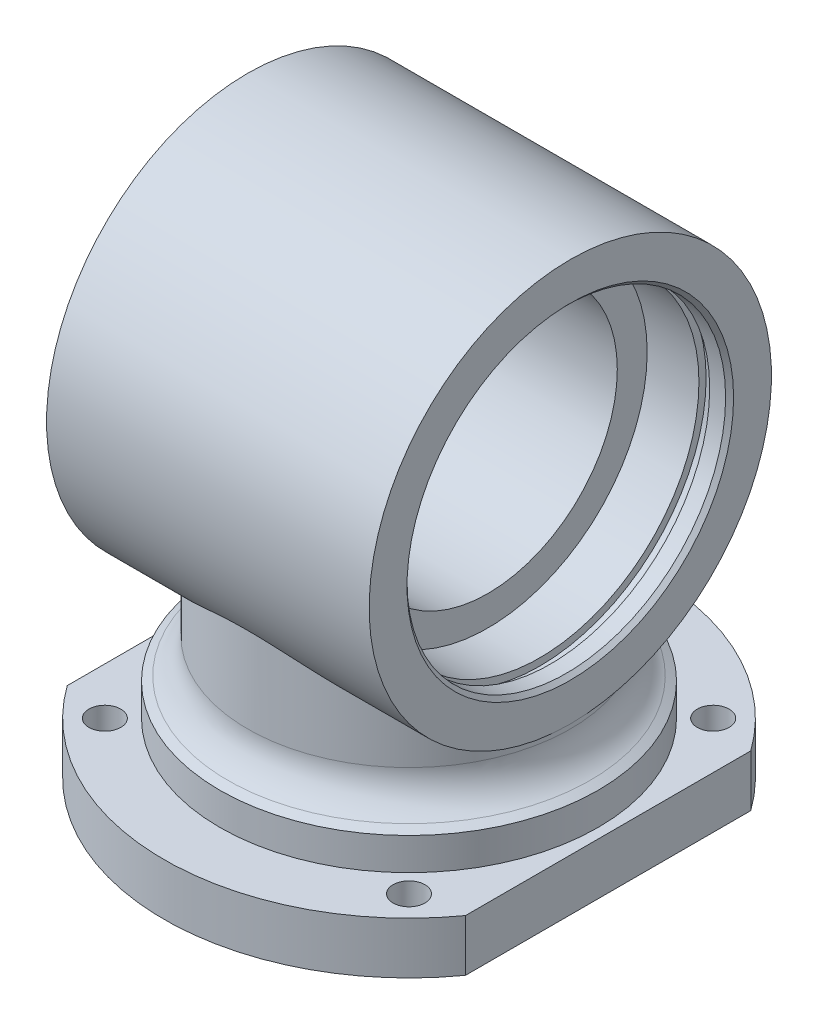
SolidWorks part; units mm, degrees
ref_plane "Front Plane" through (0, 0, 0) normal (0, 0, 1) x (1, 0, 0)
ref_plane "Top Plane" through (0, 0, 0) normal (0, 1, 0) x (1, 0, 0)
ref_plane "Right Plane" through (0, 0, 0) normal (1, 0, 0) x (0, 0, -1)
sketch "Sketch1" plane through (0, 0, 0) normal (0, 0, 1) x (1, 0, 0)
  line L0 (0, 0) -> (0, 161.3514) construction
  line L1 (0, 0) -> (-61.5, 0)
  line L2 (-61.5, 0) -> (-61.5, 13)
  line L3 (-61.5, 13) -> (-45.5, 22.2376)
  line L4 (-40.5, 30.8979) -> (-40.5, 80)
  line L5 (-40.5, 80) -> (0, 80)
  line L6 (0, 80) -> (0, 0)
  arc A0 (-45.5, 22.2376) -> (-40.5, 30.8979) centre (-50.5, 30.8979) ccw
  point P13 (-61.5, 13)
  dimension "D6" = 10
  dimension "D1" = 13
  dimension "D2" = 123
  dimension "D3" = 120
  dimension "D4" = 81
  dimension "D5" = 80
revolve "Revolve1" add sketch "Sketch1" angle 360 about L0
sketch "Sketch3" plane through (0, 0, 0) normal (1, 0, 0) x (0, 0, -1)
  line L0 (0, 0) -> (0, 82.5) construction
  circle A0 centre (0, 82.5) radius 50.5
  dimension "D1" = 101
  dimension "D2" = 82.5
extrude "Boss-Extrude1" add sketch "Sketch3" along normal mid plane 81
sketch "Sketch5" plane through (0, 0, 0) normal (0, -1, 0) x (1, 0, 0)
  line L0 (0, 0) -> (0, 94.4086) construction
  line L1 (50, -65) -> (70, -65)
  line L2 (-50, 65) -> (-70, 65)
  line L3 (-50, 65) -> (-50, -65)
  line L4 (-50, -65) -> (-70, -65)
  line L5 (-70, 65) -> (-70, -65)
  line L6 (70, 65) -> (70, -65)
  line L7 (50, 65) -> (70, 65)
  line L8 (50, 65) -> (50, -65)
  line L9 (0, 0) -> (-50, 0) construction
  dimension "D1" = 100
  dimension "D2" = 20
  dimension "D3" = 130
extrude "Cut-Extrude1" cut sketch "Sketch5" against normal blind 81
sketch "Sketch6" plane through (0, 0, 0) normal (0, 0, 1) x (1, 0, 0)
  line L0 (40.5, 82.5) -> (99.9636, 82.5) construction
  line L1 (40.5, 32) -> (40.5, 133) construction
  line L2 (-40.5, 122.5) -> (-40.5, 82.5)
  line L3 (-40.5, 133) -> (-40.5, 32) construction
  line L4 (-40.5, 122.5) -> (-35.5, 122.5)
  line L5 (0, 133) -> (0, 0) construction
  line L6 (40.5, 133) -> (-40.5, 133) construction
  line L7 (-35.5, 122.5) -> (-35.5, 124.3)
  line L8 (-35.5, 124.3) -> (-32.8, 124.3)
  line L9 (-32.8, 124.3) -> (-32.8, 122.5)
  line L10 (-32.8, 122.5) -> (32.8, 122.5)
  line L11 (-40.5, 82.5) -> (40.5, 82.5)
  line L12 (32.8, 124.3) -> (32.8, 122.5)
  line L13 (35.5, 124.3) -> (32.8, 124.3)
  line L14 (35.5, 122.5) -> (35.5, 124.3)
  line L15 (40.5, 122.5) -> (35.5, 122.5)
  line L16 (40.5, 122.5) -> (40.5, 82.5)
  line L17 (-19.8, 122.5) -> (-19.8, 115)
  line L18 (-19.8, 115) -> (19.8, 115)
  line L19 (19.8, 115) -> (19.8, 122.5)
  line L20 (0, 122.5) -> (0, 115) construction
  point P13 (0, 82.5)
  point P20 (0, 122.5)
  point P28 (32.8, 123.4)
  dimension "D1" = 5
  dimension "D2" = 80
  dimension "D3" = 83.6
  dimension "D4" = 2.7
  dimension "D5" = 13
  dimension "D6" = 65
revolve "Cut-Revolve1" cut sketch "Sketch6" angle 360 about L0 region at (0, 100.9343, 0)
sketch "Sketch7" plane through (0, 0, 0) normal (0, 0, 1) x (1, 0, 0)
  line L0 (0, 82.5) -> (40.5, 82.5) construction
  line L1 (40.5, 32) -> (40.5, 133) construction
  line L2 (0, 82.5) -> (0, 0) construction
  circle A0 centre (0, 82.5) radius 10
  dimension "D1" = 20
extrude "Cut-Extrude2" [suppressed] cut sketch "Sketch7" along normal blind 10 from offset 48.5
sketch "Sketch8" [suppressed] plane through (0, 0, 48.5) normal (0, 0, 1) x (1, 0, 0)
  circle A0 centre (0, 82.5) radius 4.5
  dimension "D1" = 9
extrude "Cut-Extrude3" [suppressed] cut sketch "Sketch8" against normal blind 20
mirror "Mirror1" [suppressed] about plane through (0, 0, 0) normal (0, 0, 1)
fillet "Fillet1" [suppressed] radius 10
sketch "Sketch9" plane through (0, 0, 0) normal (0, -1, 0) x (1, 0, 0)
  line L1 (-38.1838, -38.1838) -> (38.1838, -38.1838) construction
  line L2 (-38.1838, -38.1838) -> (-38.1838, 38.1838) construction
  line L3 (-38.1838, 38.1838) -> (38.1838, 38.1838) construction
  line L4 (38.1838, -38.1838) -> (38.1838, 38.1838) construction
  line L5 (-38.1838, -38.1838) -> (38.1838, 38.1838) construction
  line L6 (-38.1838, 38.1838) -> (38.1838, -38.1838) construction
  circle A1 centre (38.1838, 38.1838) radius 4
  circle A2 centre (-38.1838, 38.1838) radius 4
  circle A3 centre (-38.1838, -38.1838) radius 4
  circle A4 centre (38.1838, -38.1838) radius 4
  point P0 (0, 0)
  dimension "D1" = 108
  dimension "D2" = 8
extrude "Cut-Extrude4" cut sketch "Sketch9" against normal blind 20
sketch "Sketch10" plane through (0, 0, 0) normal (0, -1, 0) x (1, 0, 0)
  circle A0 centre (0, 0) radius 42.5
  dimension "D1" = 85
extrude "Cut-Extrude5" cut sketch "Sketch10" against normal blind 17
chamfer "Chamfer1" distance 1 angle 45 2 edges at (40.5, 82.5, 40) (-40.5, 82.5, 40)
sketch "Sketch11" plane through (0, 17, 0) normal (0, -1, 0) x (1, 0, 0)
  circle A0 centre (0, 0) radius 30 construction
  circle A1 centre (0, 30) radius 3
  circle A2 centre (30, 0) radius 3
  circle A3 centre (0, -30) radius 3
  circle A4 centre (-30, 0) radius 3
  point P14 (0, 0)
  dimension "D1" = 60
  dimension "D2" = 6
  dimension "D3" = 4
extrude "Cut-Extrude6" [suppressed] cut sketch "Sketch11" against normal through all
chamfer "Chamfer2" distance 3 angle 45 1 edges at (0, 17, -42.5)
sketch "Sketch13" plane through (0, 0, 0) normal (0, -1, 0) x (1, 0, 0)
  circle A0 centre (0, 0) radius 47.5
  dimension "D1" = 95
extrude "Cut-Extrude8" cut sketch "Sketch13" against normal blind 10 from offset 13 flip side to cut offset against normal yes
